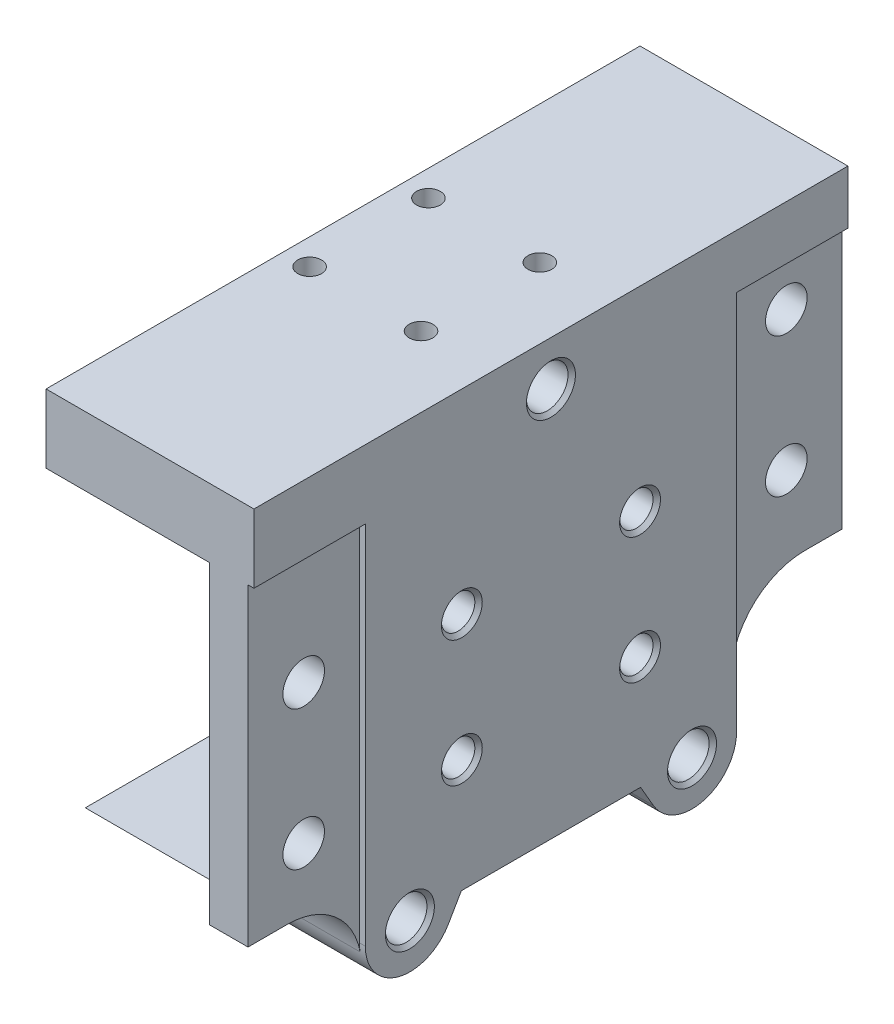
SolidWorks part; units mm, degrees
material "PET"
ref_plane "Front Plane" through (0, 0, 0) normal (0, 0, 1) x (1, 0, 0)
ref_plane "Top Plane" through (0, 0, 0) normal (0, 1, 0) x (1, 0, 0)
ref_plane "Right Plane" through (0, 0, 0) normal (1, 0, 0) x (0, 0, -1)
sketch "Sketch1" plane through (0, 0, 0) normal (0, 0, 1) x (1, 0, 0)
  line L0 (-11, 0) -> (17, 0)
  line L1 (17, 0) -> (17, 54)
  line L2 (17, 54) -> (-11, 54)
  line L3 (11, 47) -> (11, 7)
  line L4 (11, 7) -> (-11, 7)
  line L8 (-11, 7) -> (-11, 0)
  line L9 (11, 47) -> (-11, 47)
  line L10 (-11, 47) -> (-11, 54)
  line L11 (0, 0) -> (0, 42.7189) construction
  point P11 (0, 7)
  dimension "D1" = 7
  dimension "D2" = 22
  dimension "D3" = 6
  dimension "D4" = 7
  dimension "D5" = 40
extrude "Boss-Extrude1" add sketch "Sketch1" along normal blind 50
sketch "Sketch2" plane through (0, 0, 0) normal (0, -1, 0) x (1, 0, 0)
  line L0 (-11, 50) -> (-11, 0) construction
  line L3 (-7.5, 17) -> (7.5, 17) construction
  line L4 (-7.5, 17) -> (-7.5, 33) construction
  line L5 (-7.5, 33) -> (7.5, 33) construction
  line L6 (7.5, 17) -> (7.5, 33) construction
  line L7 (-7.5, 17) -> (7.5, 33) construction
  line L8 (-7.5, 33) -> (7.5, 17) construction
  point P5 (0, 25)
  dimension "D1" = 15
  dimension "D2" = 16
  dimension "D3" = 11
  dimension "D4" = 25
hole_wizard "Ø3.2 (3.2) Diameter Hole1" positions "Sketch3" profile "Sketch4" hole size "Ø3.2" standard "ANSI Metric" end condition through all
sketch "Sketch3" plane through (0, 0, 0) normal (0, -1, 0) x (-1, 0, 0)
  point P0 (-7.5, -17)
  point P3 (7.5, -17)
  point P6 (7.5, -33)
  point P9 (-7.5, -33)
sketch "Sketch4" plane through (7.5, 0, 17) normal (1, 0, 0) x (0, 0, -1)
  line L0 (0, 0) -> (0, 54)
  line L1 (0, 54) -> (1.6, 54)
  line L2 (1.6, 54) -> (1.6, 0)
  line L5 (1.6, 0) -> (0, 0)
  line L11 (0, -6.35) -> (0, 107.95) construction
  dimension "Thru Hole Dia." = 3.2
  dimension "Thru Hole Depth" = 54
sketch "Sketch5" plane through (17, 0, 0) normal (1, 0, 0) x (0, 0, -1)
  line L0 (-50, 32.25) -> (0, 32.25) construction
  line L1 (-50, 0) -> (-50, 54) construction
  line L2 (0, 0) -> (0, 54) construction
  line L4 (-50, 15.25) -> (0, 15.25) construction
  line L5 (-13, 32.25) -> (-13, 15.25) construction
  line L6 (-37, 32.25) -> (-37, 15.25) construction
  line L7 (-50, 0) -> (0, 0) construction
  circle A0 centre (-37, 32.25) radius 2.25
  circle A1 centre (-13, 32.25) radius 2.25
  circle A2 centre (-37, 15.25) radius 2.25
  circle A3 centre (-13, 15.25) radius 2.25
  point P12 (-25, 32.25)
  dimension "D2" = 12
  dimension "D3" = 12
  dimension "D4" = 4.5
  dimension "D5" = 4.5
  dimension "D7" = 4.5
  dimension "D8" = 4.5
  dimension "D1" = 15.25
  dimension "D6" = 17
extrude "Cut-Extrude1" cut sketch "Sketch5" against normal through all
sketch "Sketch6" plane through (17, 0, 0) normal (1, 0, 0) x (0, 0, -1)
  line L1 (-50, 54) -> (-65, 54)
  line L2 (-50, 54) -> (-50, 49.25)
  line L3 (-50, 49.25) -> (-65, 49.25)
  line L4 (-65, 54) -> (-65, 49.25)
  line L5 (0, 54) -> (15, 54)
  line L6 (0, 54) -> (0, 49.25)
  line L7 (0, 49.25) -> (15, 49.25)
  line L8 (15, 54) -> (15, 49.25)
  dimension "D1" = 4.75
  dimension "D2" = 15
  dimension "D3" = 15
extrude "Boss-Extrude2" add sketch "Sketch6" against normal up to surface (28 mm away) up to face at (-11, 50.5, 25)
ref_plane "Plane1" through (0, 0, 25) normal (0, 0, -1) x (-1, 0, 0)
sketch "Sketch8" plane through (0, 54, 0) normal (0, 1, 0) x (1, 0, 0)
  line L0 (-11, 15) -> (17, 15) construction
  line L1 (-5.6, 15) -> (6.6, 15)
  line L2 (-5.6, 15) -> (-5.6, -65)
  line L4 (6.6, 15) -> (6.6, -65)
  line L5 (-11, -65) -> (17, -65) construction
  line L6 (-5.6, -65) -> (6.6, -65)
  line L10 (-11, -65) -> (-11, 15) construction
  dimension "D1" = 12.2
  dimension "D3" = 5.4
extrude "Boss-Extrude3" add sketch "Sketch8" along normal blind 25
sketch "Sketch9" plane through (-5.6, 0, 0) normal (-1, 0, 0) x (0, 0, 1)
  line L0 (-7.5, 79) -> (-7.5, 54) construction
  line L2 (-15, 54) -> (65, 54) construction
  line L3 (57.5, 79) -> (57.5, 54) construction
  line L6 (-7.5, 66.2) -> (57.5, 66.2) construction
  line L7 (65, 54) -> (-15, 54) construction
  line L9 (-15, 79) -> (-15, 54) construction
  line L10 (-15, 54) -> (65, 54) construction
  line L11 (-15, 79) -> (65, 79) construction
  line L12 (65, 79) -> (65, 54) construction
  circle A0 centre (-7.5, 66.2) radius 2.75
  circle A1 centre (57.5, 66.2) radius 2.75
  dimension "D2" = 5.5
  dimension "D3" = 5.5
  dimension "D1" = 12.2
  dimension "D4" = 7.5
  dimension "D5" = 7.5
extrude "Cut-Extrude2" cut sketch "Sketch9" against normal through all
sketch "Sketch10" plane through (-11, 0, 0) normal (-1, 0, 0) x (0, 0, 1)
  line L0 (50, 0) -> (0, 0) construction
  line L1 (0, 7) -> (0, 0) construction
  line L2 (11.1962, -3) -> (12.9282, 0)
  line L3 (25, 0) -> (25, 52.5) construction
  line L4 (22, 57.6962) -> (15.5981, 54)
  line L5 (65, 54) -> (-15, 54) construction
  line L6 (28, 57.6962) -> (34.4019, 54)
  line L7 (38.8038, -3) -> (37.0718, 0)
  line L8 (0, 0) -> (12.9282, 0)
  line L9 (37.0718, 0) -> (50, 0)
  line L10 (15.5981, 54) -> (34.4019, 54)
  arc A0 (0, 0) -> (11.1962, -3) centre (6, 0) ccw
  arc A1 (38.8038, -3) -> (50, 0) centre (44, 0) ccw
  arc A2 (28, 57.6962) -> (22, 57.6962) centre (25, 52.5) ccw
  dimension "D1" = 12
  dimension "D2" = 12
  dimension "D3" = 12
  dimension "D4" = 52.5
  dimension "D5" = 30
  dimension "D6" = 30
  dimension "D7" = 60
  dimension "D8" = 60
extrude "Boss-Extrude4" add sketch "Sketch10" against normal up to surface (28 mm away) up to face at (17, 34.5, 13)
sketch "Sketch11" plane through (-11, 0, 0) normal (-1, 0, 0) x (0, 0, 1)
  circle A0 centre (25, 52.5) radius 2.8
  circle A1 centre (44, 0) radius 2.8
  circle A2 centre (6, 0) radius 2.8
  dimension "D1" = 5.6
  dimension "D2" = 5.6
  dimension "D3" = 5.6
extrude "Cut-Extrude3" cut sketch "Sketch11" against normal up to next
chamfer "Chamfer1" distance 0.5 angle 45 18 edges at (6.6, 66.2, -4.75) (6.6, 66.2, 60.25) (17, 49.7, 25) (17, 17.5, 13) (17, 34.5, 13) (17, 34.5, 37) (17, 17.5, 37) (17, -2.8, 44) (17, -2.8, 6) (-11, -2.8, 6) (-11, -2.8, 44) (11, 17.5, 37) (11, 34.5, 37) (11, 34.5, 13) (11, 17.5, 13) (-11, 49.7, 25) (-5.6, 66.2, 60.25) (-5.6, 66.2, -4.75)
sketch "Sketch12" plane through (6.6, 0, 0) normal (1, 0, 0) x (0, 0, -1)
  line L0 (-65, 54) -> (-34.4019, 54)
  line L1 (-34.4019, 54) -> (-28, 57.6962)
  line L2 (-65, 54) -> (-65, 79)
  line L3 (-65, 79) -> (15, 79)
  line L4 (15, 79) -> (15, 54)
  line L5 (15, 54) -> (-15.5981, 54)
  line L6 (-15.5981, 54) -> (-22, 57.6962)
  arc A0 (-28, 57.6962) -> (-22, 57.6962) centre (-25, 52.5) cw
extrude "Cut-Extrude4" cut sketch "Sketch12" against normal through all
sketch "Sketch14" plane through (11, 0, 0) normal (-1, 0, 0) x (0, 0, 1)
  line L0 (65, 49.25) -> (65, 54) construction
  line L1 (50, 47) -> (65, 47)
  line L2 (50, 47) -> (50, 7)
  line L3 (50, 7) -> (65, 7)
  line L4 (65, 47) -> (65, 7)
  dimension "D1" = 40
extrude "Boss-Extrude5" add sketch "Sketch14" against normal blind 5.2
sketch "Sketch16" plane through (17, 0, 0) normal (1, 0, 0) x (0, 0, -1)
  line L0 (0, 0) -> (0, 49.25) construction
  line L1 (15, 54) -> (0, 54)
  line L2 (15, 54) -> (15, 37)
  line L3 (15, 37) -> (0, 37)
  line L4 (0, 54) -> (0, 37)
  dimension "D1" = 17
extrude "Cut-Extrude6" cut sketch "Sketch16" against normal through all
sketch "Sketch18" plane through (11, 0, 0) normal (-1, 0, 0) x (0, 0, 1)
  line L0 (0, 47) -> (0, 7) construction
  line L1 (0, 15.75) -> (-15, 15.75)
  line L2 (0, 15.75) -> (0, 51.25)
  line L3 (0, 51.25) -> (-15, 51.25)
  line L4 (-15, 15.75) -> (-15, 51.25)
  line L5 (50, 47) -> (0, 47) construction
  dimension "D1" = 31.25
  dimension "D2" = 4.25
  dimension "D3" = 15
extrude "Boss-Extrude6" add sketch "Sketch18" against normal blind 5.2
sketch "Sketch20" plane through (-11, 0, 0) normal (-1, 0, 0) x (0, 0, 1)
  line L0 (15.5981, 54) -> (0, 54) construction
  line L1 (0, 58.25) -> (7.799, 58.25)
  line L2 (0, 58.25) -> (0, 54)
  line L3 (0, 54) -> (7.799, 54)
  line L4 (7.799, 58.25) -> (7.799, 54)
  line L5 (0, 51.25) -> (-15, 51.25) construction
  line L6 (0, 54) -> (0, 47) construction
  dimension "D1" = 7
extrude "Boss-Extrude7" add sketch "Sketch20" against normal up to surface (27.2 mm away) up to face at (16.2, 33.5, -7.5)
fillet "Fillet1" radius 10 2 edges at (13.6, 7, 50) (13.6, 15.75, 0)
sketch "Sketch21" plane through (16.2, 0, 0) normal (1, 0, 0) x (0, 0, -1)
  line L0 (-65, 54) -> (-34.4019, 54) construction
  line L1 (-61.2082, 30.25) -> (-54.4505, 30.25)
  line L2 (-61.2082, 30.25) -> (-61.2082, 19.25)
  line L3 (-61.2082, 19.25) -> (-54.4505, 19.25)
  line L4 (-54.4505, 30.25) -> (-54.4505, 19.25)
  dimension "D1" = 11
  dimension "D2" = 34.75
sketch "Sketch22" plane through (16.2, 0, 0) normal (1, 0, 0) x (0, 0, -1)
  line L0 (-61.2082, 30.25) -> (-54.4505, 30.25) construction
  line L1 (-65, 47) -> (-50, 47) construction
  line L2 (-61.2082, 19.25) -> (-54.4505, 19.25) construction
  line L3 (-57.5, 47) -> (-57.5, 14.4567) construction
  circle A0 centre (-57.5, 34.125) radius 2.8
  circle A1 centre (-57.5, 15.375) radius 2.8
  dimension "D1" = 5.6
  dimension "D2" = 3.875
  dimension "D3" = 5.6
  dimension "D4" = 3.875
extrude "Cut-Extrude8" cut sketch "Sketch22" against normal through all
sketch "Sketch23" plane through (11, 0, 0) normal (-1, 0, 0) x (0, 0, 1)
  line L1 (-11.8631, 41.25) -> (-3.2765, 41.25)
  line L2 (-11.8631, 41.25) -> (-11.8631, 30.25)
  line L3 (-11.8631, 30.25) -> (-3.2765, 30.25)
  line L4 (-3.2765, 41.25) -> (-3.2765, 30.25)
  line L5 (15.5981, 54) -> (0, 54) construction
  dimension "D1" = 11
  dimension "D3" = 23.75
sketch "Sketch24" plane through (11, 0, 0) normal (-1, 0, 0) x (0, 0, 1)
  line L0 (-7.5, 51.25) -> (-7.5, 15.4325) construction
  line L1 (0, 51.25) -> (-15, 51.25) construction
  line L2 (-11.8631, 41.25) -> (-3.2765, 41.25) construction
  line L3 (-11.8631, 30.25) -> (-3.2765, 30.25) construction
  arc A0 (-0.0784, 7) -> (-10, 15.75) centre (-10, 5.75) ccw construction
  circle A1 centre (-7.5, 45.125) radius 2.8
  circle A2 centre (-7.5, 26.375) radius 2.8
  dimension "D1" = 5.6
  dimension "D2" = 3.875
  dimension "D3" = 3.875
  dimension "D4" = 5.6
extrude "Cut-Extrude9" cut sketch "Sketch24" against normal through all
sketch "Sketch26" plane through (17, 0, 0) normal (1, 0, 0) x (0, 0, -1)
  line L0 (-7.799, 58.5) -> (-25, 58.5)
  line L1 (-7.799, 58.5) -> (-7.799, 54)
  line L2 (-7.799, 54) -> (-15.5981, 54)
  line L3 (-15.5981, 54) -> (-22, 57.6962)
  arc A0 (-22, 57.6962) -> (-28, 57.6962) centre (-25, 52.5) ccw construction
  arc A1 (-25, 58.5) -> (-22, 57.6962) centre (-25, 52.5) cw
extrude "Boss-Extrude9" add sketch "Sketch26" against normal up to surface (28 mm away) up to face at (-11, 0, 2.7)
sketch "Sketch29" plane through (0, 54, 0) normal (0, 1, 0) x (1, 0, 0)
  circle A0 centre (-7.5, -33) radius 3.75
  circle A1 centre (7.5, -33) radius 3.75
  circle A2 centre (-7.5, -17) radius 1.6
  circle A3 centre (7.5, -17) radius 1.6
  dimension "D1" = 7.5
  dimension "D2" = 7.5
  dimension "D3" = 3.2
  dimension "D4" = 3.2
extrude "Cut-Extrude11" cut sketch "Sketch29" along normal blind 10
sketch "Sketch28" plane through (16.2, 0, 0) normal (1, 0, 0) x (0, 0, -1)
  line L1 (-65, 47) -> (-50, 47)
  line L2 (-65, 47) -> (-65, 49.25)
  line L3 (-65, 49.25) -> (-50, 49.25)
  line L4 (-50, 47) -> (-50, 49.25)
extrude "Boss-Extrude10" add sketch "Sketch28" against normal up to surface (5.2 mm away) up to face at (11, 45.125, -4.7)
sketch "Sketch30" plane through (17, 0, 0) normal (1, 0, 0) x (0, 0, -1)
  line L1 (0, 54) -> (-7.799, 54)
  line L2 (0, 54) -> (0, 58.5)
  line L3 (0, 58.5) -> (-7.799, 58.5)
  line L4 (-7.799, 54) -> (-7.799, 58.5)
extrude "Boss-Extrude11" add sketch "Sketch30" against normal up to surface (28 mm away) up to face at (-11, 55.8, 25)
sketch "Sketch31" plane through (17, 0, 0) normal (1, 0, 0) x (0, 0, -1)
  line L0 (0, 0) -> (0, 58.5) construction
  line L1 (15, 51.25) -> (0, 51.25)
  line L2 (15, 51.25) -> (15, 58.5)
  line L3 (15, 58.5) -> (0, 58.5)
  line L4 (0, 51.25) -> (0, 58.5)
extrude "Boss-Extrude12" add sketch "Sketch31" against normal up to surface (28 mm away) up to face at (-11, 53.3086, 34.5734)
sketch "Sketch32" plane through (-11, 0, 0) normal (-1, 0, 0) x (0, 0, 1)
  line L0 (25, 58.5) -> (25, 55.8)
  line L1 (65, 54) -> (27.9394, 54)
  line L2 (25, 58.5) -> (65, 58.5)
  line L3 (65, 58.5) -> (65, 54)
  arc A0 (27.9394, 54) -> (25, 55.8) centre (25, 52.5) ccw
extrude "Boss-Extrude14" add sketch "Sketch32" against normal up to surface (28 mm away) up to face at (17, 31.2868, 25.8303)
sketch "Sketch33" plane through (0, 47, 0) normal (0, -1, 0) x (1, 0, 0)
  circle A0 centre (-7.5, 33) radius 1.6
  circle A1 centre (7.5, 33) radius 1.6
extrude "Cut-Extrude12" cut sketch "Sketch33" against normal through all
